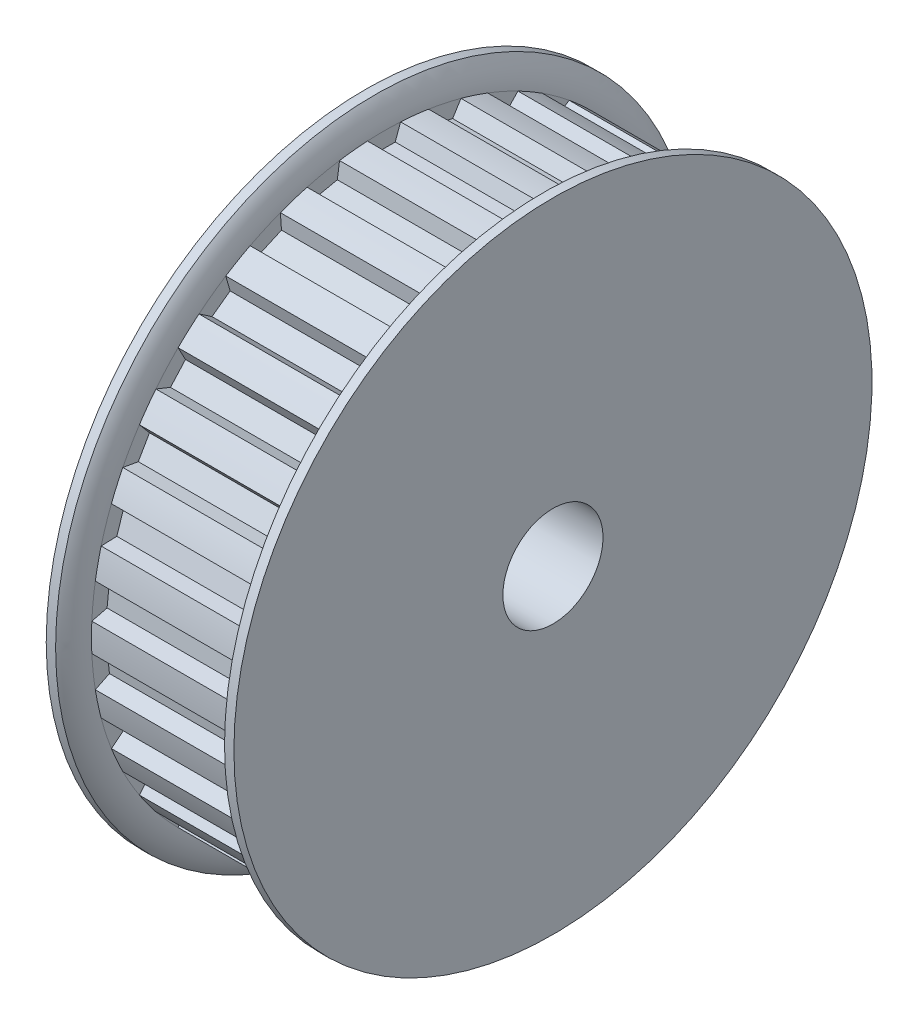
SolidWorks part; units mm, degrees
ref_plane "Front Plane" through (0, 0, 0) normal (0, 0, 1) x (1, 0, 0)
ref_plane "Top Plane" through (0, 0, 0) normal (0, 1, 0) x (1, 0, 0)
ref_plane "Right Plane" through (0, 0, 0) normal (1, 0, 0) x (0, 0, -1)
sketch "Sketch1" plane through (0, 0, 0) normal (1, 0, 0) x (0, 0, -1)
  line L3 (0, 0) -> (0, 22.18) construction
  line L6 (0, 22.18) -> (0, 23.38) construction
  line L7 (-1.325, 23.3424) -> (-0.8953, 22.1619)
  line L8 (1.325, 23.3424) -> (0.8953, 22.1619)
  line L9 (0, -2.2) -> (0, -3.2) construction
  line L10 (0, 23.88) -> (0, 23.38) construction
  line L12 (-0.8953, 22.1619) -> (0.8953, 22.1619)
  line L15 (0, 0) -> (0, -2.2) construction
  circle A0 centre (0, 0) radius 23.88 construction
  circle A1 centre (0, 0) radius 22.18 construction
  arc A7 (1.325, 23.3424) -> (-1.325, 23.3424) centre (0, 0) ccw
  dimension "PD" = 47.76
  dimension "D1" = 40
  dimension "D3" = 0.5
  dimension "D2" = 1.2
  dimension "D4" = 2.65
sketch "Sketch2" plane through (0, 0, 0) normal (0, 0, 1) x (1, 0, 0)
  line L0 (-10.5, 0) -> (10.5, 0) construction
  line L1 (-10.5, 4) -> (10.5, 4)
  line L2 (-10.5, 4) -> (-10.5, 17)
  line L3 (-4.5, 25.5) -> (-3.75, 25.5)
  line L4 (-3, 23.38) -> (-4.5, 23.38) construction
  line L5 (9.75, 23.38) -> (9.75, 25.5) construction
  line L6 (-3, 23.38) -> (9, 23.38)
  line L8 (9, 23.38) -> (10.5, 23.38) construction
  line L9 (9.75, 25.5) -> (10.5, 25.5)
  line L10 (10.5, 25.5) -> (10.5, 4)
  line L12 (-7.5, 17) -> (-7.5, 4) construction
  line L13 (-4.5, 25.5) -> (-4.5, 17)
  line L14 (-4.5, 17) -> (-10.5, 17)
  arc A0 (9, 23.38) -> (9.75, 25.5) centre (12.3713, 23.38) cw
  arc A1 (-3, 23.38) -> (-3.75, 25.5) centre (-6.3713, 23.38) ccw
  point P19 (-3, 23.38)
  point P20 (9, 23.38)
  dimension "Bore Size" = 8
  dimension "Overall Width" = 21
  dimension "Inside Width" = 12
  dimension "Outside Width" = 15
  dimension "Hub Dia" = 34
  dimension "OD" = 51
sketch "Sketch6" plane through (0, 0, 0) normal (0, 0, 1) x (1, 0, 0)
  line L0 (9.75, 25.5) -> (10.5, 25.5) construction
  line L1 (-3, 23.38) -> (9, 23.38) construction
  line L2 (-4.5, 25.5) -> (-3.75, 25.5) construction
  line L3 (-4.5, 25.5) -> (-4.5, 17) construction
  line L4 (-4.5, 17) -> (-10.5, 17) construction
  line L5 (-10.5, 4) -> (-10.5, 17) construction
  line L6 (-10.5, 4) -> (10.5, 4) construction
  line L7 (10.5, 25.5) -> (10.5, 4) construction
  line L8 (9.75, 25.5) -> (10.5, 25.5)
  line L9 (-3, 23.38) -> (9, 23.38)
  line L10 (-4.5, 25.5) -> (-3.75, 25.5)
  line L11 (-4.5, 25.5) -> (-4.5, 17)
  line L12 (-4.5, 17) -> (-10.5, 17)
  line L13 (-10.5, 4) -> (-10.5, 17)
  line L14 (-10.5, 4) -> (10.5, 4)
  line L15 (10.5, 25.5) -> (10.5, 4)
  arc A0 (9.75, 25.5) -> (9, 23.38) centre (12.3713, 23.38) ccw construction
  arc A1 (-3, 23.38) -> (-3.75, 25.5) centre (-6.3713, 23.38) ccw construction
  arc A2 (9.75, 25.5) -> (9, 23.38) centre (12.3713, 23.38) ccw
  arc A3 (-3, 23.38) -> (-3.75, 25.5) centre (-6.3713, 23.38) ccw
revolve "Revolve1" add sketch "Sketch6" angle 360 about L0
sketch "Sketch3" plane through (0, 0, 0) normal (1, 0, 0) x (0, 0, -1)
  line L2 (-1.325, 23.3424) -> (-0.8953, 22.1619) construction
  line L3 (-0.8953, 22.1619) -> (0.8953, 22.1619) construction
  line L4 (1.325, 23.3424) -> (0.8953, 22.1619) construction
  line L5 (-1.325, 23.3424) -> (-0.8953, 22.1619)
  line L6 (-0.8953, 22.1619) -> (0.8953, 22.1619)
  line L7 (1.325, 23.3424) -> (0.8953, 22.1619)
  arc A1 (1.325, 23.3424) -> (-1.325, 23.3424) centre (0, 0) ccw construction
  arc A2 (1.325, 23.3424) -> (-1.325, 23.3424) centre (0, 0) ccw
extrude "Cut-Extrude1" cut sketch "Sketch3" along normal up to vertex (9 mm away) from vertex up to point (9, 23.38, 0) starting at point (-3, 23.38, 0)
pattern_circular "CirPattern1" count 30 over 360 about axis through (-10.5, 0, 0) along (-1, 0, 0) of "Cut-Extrude1"
sketch "Sketch5" plane through (0, 0, 0) normal (0, 0, 1) x (1, 0, 0)
  line L0 (-10.5, 0) -> (10.5, 0) construction
  point P0 (9, 0)
ref_axis "Center Axis 1" through (10.5, 0, 0) along (-1, 0, 0)
equation "\"D3@Sketch1\" = \"ht@Sketch1\" / 2"
equation "\"D2@Sketch1\" = \"hs@Sketch1\" - \"ht@Sketch1\""
